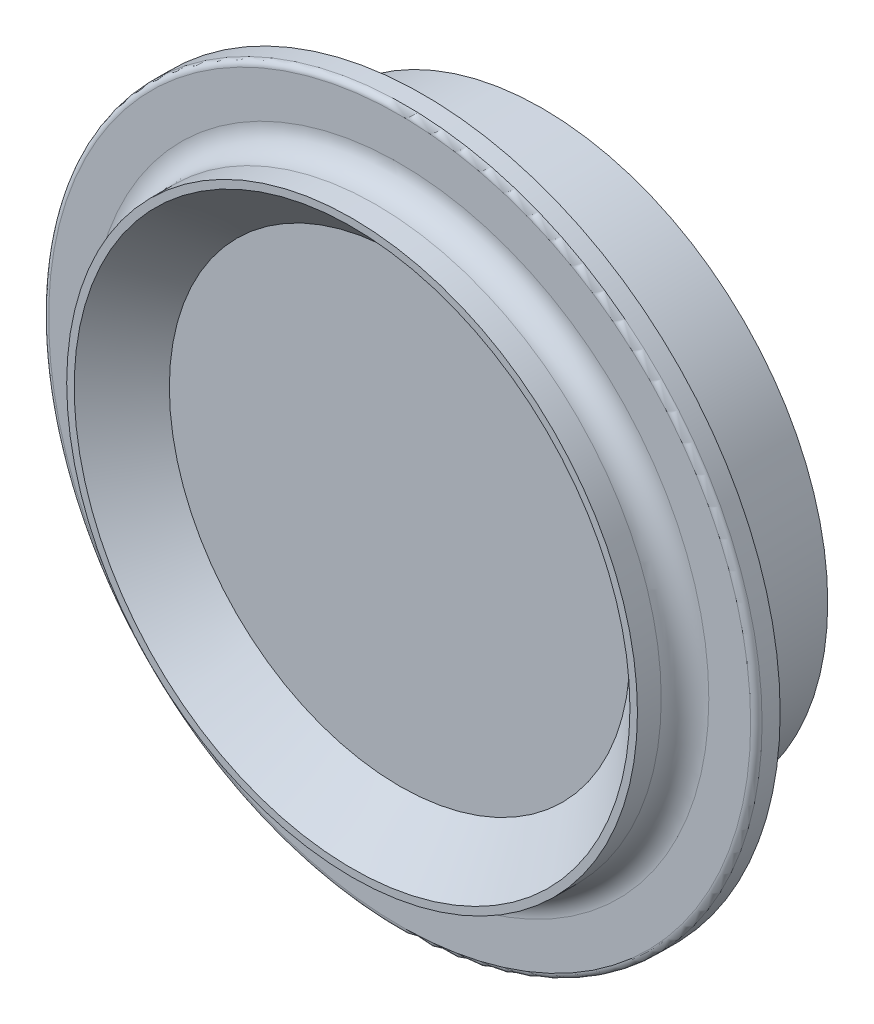
SolidWorks part; units mm, degrees
material "AISI 304"
ref_plane "Front Plane" through (0, 0, 0) normal (0, 0, 1) x (1, 0, 0)
ref_plane "Top Plane" through (0, 0, 0) normal (0, 1, 0) x (1, 0, 0)
ref_plane "Right Plane" through (0, 0, 0) normal (1, 0, 0) x (0, 0, -1)
sketch "Sketch1" plane through (0, 0, 0) normal (0, 0, 1) x (1, 0, 0)
  line L0 (358.31, 263.2027) -> (358.3777, 263.0051)
  line L1 (356.948, 250.8986) -> (358.2723, 250.7125)
  line L2 (358.2581, 250.6141) -> (356.9329, 250.8003)
  line L3 (357.1896, 254.7211) -> (358.5268, 254.7444)
  line L4 (358.5281, 254.645) -> (357.1902, 254.6217)
  line L5 (356.8304, 258.5343) -> (358.1474, 258.7666)
  line L6 (358.1643, 258.6686) -> (356.8464, 258.4362)
  line L7 (323.9266, 279.871) -> (324.1241, 279.9387)
  line L8 (332.4082, 278.7506) -> (332.3848, 280.0878)
  line L9 (332.4842, 280.0891) -> (332.5076, 278.7512)
  line L10 (353.9034, 247.6991) -> (353.8718, 247.5995)
  line L11 (353.8718, 247.5995) -> (355.116, 247.2047)
  line L12 (355.1477, 247.3043) -> (353.9034, 247.6991)
  line L13 (353.093, 245.5279) -> (353.0512, 245.4322)
  line L14 (343.2276, 272.3738) -> (344.5485, 274.6256)
  line L15 (344.7287, 274.52) -> (343.4077, 272.2681)
  line L16 (343.4077, 272.2681) -> (343.2276, 272.3738)
  line L17 (341.8816, 274.5301) -> (342.4208, 275.7188)
  line L18 (342.5159, 275.6757) -> (341.9767, 274.4869)
  line L19 (341.9767, 274.4869) -> (341.8816, 274.5301)
  line L20 (344.5704, 278.6579) -> (344.758, 278.5661)
  line L21 (344.758, 278.5661) -> (343.6107, 276.2211)
  line L22 (343.4231, 276.3128) -> (344.5704, 278.6579)
  line L23 (343.529, 276.2613) -> (344.1153, 277.4633)
  line L24 (344.2045, 277.4193) -> (343.6107, 276.2211)
  line L25 (353.6191, 254.3151) -> (356.2297, 254.2971)
  line L26 (356.2284, 254.0882) -> (353.6177, 254.1063)
  line L27 (353.6177, 254.1063) -> (353.6191, 254.3151)
  line L28 (354.8237, 256.455) -> (354.8135, 256.559)
  line L29 (354.8135, 256.559) -> (356.1126, 256.6864)
  line L30 (356.1229, 256.5825) -> (354.8237, 256.455)
  line L31 (347.6738, 270.7309) -> (348.5539, 271.6948)
  line L32 (348.6311, 271.6245) -> (347.7509, 270.6605)
  line L33 (347.7509, 270.6605) -> (347.6738, 270.7309)
  line L34 (345.9635, 272.1355) -> (345.8795, 272.1975)
  line L35 (345.8795, 272.1975) -> (346.654, 273.2482)
  line L36 (346.7381, 273.1863) -> (345.9635, 272.1355)
  line L37 (355.7611, 259.0098) -> (354.4824, 258.7472)
  line L38 (354.4614, 258.8495) -> (355.7401, 259.1121)
  line L39 (353.8718, 261.0908) -> (355.116, 261.4855)
  line L40 (355.1477, 261.386) -> (353.9034, 260.9912)
  line L41 (354.4824, 258.7472) -> (354.4614, 258.8495)
  line L42 (353.9034, 260.9912) -> (353.8718, 261.0908)
  line L43 (353.093, 263.1624) -> (353.0512, 263.2581)
  line L44 (353.0512, 263.2581) -> (354.2473, 263.7807)
  line L45 (354.2892, 263.6851) -> (353.093, 263.1624)
  line L46 (350.8428, 264.7366) -> (353.1126, 266.0263)
  line L47 (353.2159, 265.8448) -> (350.9459, 264.555)
  line L48 (350.9459, 264.555) -> (350.8428, 264.7366)
  line L49 (349.3744, 269.0066) -> (349.305, 269.0847)
  line L50 (350.816, 267.1921) -> (350.7552, 267.2771)
  line L51 (350.7552, 267.2771) -> (351.8165, 268.037)
  line L52 (351.8774, 267.9521) -> (350.816, 267.1921)
  line L53 (349.305, 269.0847) -> (350.2811, 269.9514)
  line L54 (350.3505, 269.8734) -> (349.3744, 269.0066)
  line L55 (354.4614, 249.8407) -> (355.7401, 249.5782)
  line L56 (355.7611, 249.6805) -> (354.4824, 249.943)
  line L57 (354.4824, 249.943) -> (354.4614, 249.8407)
  line L58 (354.8135, 252.1313) -> (356.1126, 252.0038)
  line L59 (356.1229, 252.1078) -> (354.8237, 252.2352)
  line L60 (354.8237, 252.2352) -> (354.8135, 252.1313)
  line L61 (354.3589, 265.76) -> (355.5397, 266.3878)
  line L62 (355.5861, 266.2999) -> (354.4045, 265.6716)
  line L63 (352.3076, 268.9945) -> (353.3757, 269.7993)
  line L64 (353.4352, 269.7197) -> (352.3665, 268.9143)
  line L65 (349.7756, 271.8683) -> (350.7046, 272.8303)
  line L66 (350.7758, 272.7609) -> (349.8463, 271.7983)
  line L67 (346.8252, 274.3106) -> (347.5922, 275.4061)
  line L68 (347.6735, 275.3487) -> (346.9059, 274.2526)
  line L69 (328.2797, 276.0224) -> (328.0172, 277.3011)
  line L70 (328.1195, 277.3221) -> (328.382, 276.0434)
  line L71 (328.382, 276.0434) -> (328.2797, 276.0224)
  line L72 (323.9669, 274.654) -> (323.8712, 274.6122)
  line L73 (326.0385, 275.4328) -> (325.6437, 276.677)
  line L74 (325.7433, 276.7087) -> (326.1381, 275.4644)
  line L75 (326.1381, 275.4644) -> (326.0385, 275.4328)
  line L76 (324.8849, 277.44) -> (324.4495, 278.7044)
  line L77 (333.041, 277.7894) -> (333.023, 275.1787)
  line L78 (332.8141, 275.1801) -> (332.8322, 277.7907)
  line L79 (330.5703, 276.3745) -> (330.4428, 277.6736)
  line L80 (330.5468, 277.6839) -> (330.6742, 276.3847)
  line L81 (333.023, 275.1787) -> (332.8141, 275.1801)
  line L82 (330.6742, 276.3847) -> (330.5703, 276.3745)
  line L83 (337.4861, 275.9804) -> (337.7663, 277.2553)
  line L84 (337.8683, 277.233) -> (337.5881, 275.958)
  line L85 (337.5881, 275.958) -> (337.4861, 275.9804)
  line L86 (335.1988, 276.3534) -> (335.3443, 277.6506)
  line L87 (335.4481, 277.639) -> (335.3026, 276.3418)
  line L88 (335.3026, 276.3418) -> (335.1988, 276.3534)
  line L89 (339.8209, 275.3375) -> (339.7219, 275.3704)
  line L90 (339.7219, 275.3704) -> (340.1338, 276.609)
  line L91 (340.2329, 276.5761) -> (339.8209, 275.3375)
  line L92 (324.7735, 277.4015) -> (323.9266, 279.871)
  line L93 (324.1241, 279.9387) -> (324.971, 277.4693)
  line L94 (328.5949, 278.3914) -> (328.3627, 279.7084)
  line L95 (328.4607, 279.7253) -> (328.6931, 278.4074)
  line L96 (324.5436, 278.7365) -> (324.971, 277.4693)
  line L97 (336.2307, 278.509) -> (336.4168, 279.8333)
  line L98 (336.5152, 279.8191) -> (336.3289, 278.4939)
  line L99 (339.9683, 277.6723) -> (340.3593, 278.9512)
  line L100 (340.4543, 278.9218) -> (340.063, 277.6421)
  line L101 (356.1113, 247.161) -> (357.3902, 246.77)
  line L102 (357.3608, 246.675) -> (356.0811, 247.0662)
  line L103 (358.3777, 263.0051) -> (355.9083, 262.1582)
  line L104 (355.8405, 262.3558) -> (358.31, 263.2027)
  line L105 (355.879, 262.2444) -> (357.1434, 262.6798)
  line L106 (357.1755, 262.5857) -> (355.9083, 262.1582)
  line L107 (357.0969, 242.5589) -> (357.0051, 242.3713)
  line L108 (343.2276, 236.3165) -> (344.5485, 234.0647)
  line L109 (344.7287, 234.1703) -> (343.4077, 236.4222)
  line L110 (343.4077, 236.4222) -> (343.2276, 236.3165)
  line L111 (341.6417, 228.8193) -> (341.4441, 228.7515)
  line L112 (341.4441, 228.7515) -> (340.5972, 231.221)
  line L113 (340.7948, 231.2888) -> (341.6417, 228.8193)
  line L114 (340.5972, 231.221) -> (340.2891, 232.1331)
  line L115 (340.6834, 231.2503) -> (341.1188, 229.9858)
  line L116 (341.0247, 229.9538) -> (340.5972, 231.221)
  line L117 (344.199, 232.7703) -> (344.8268, 231.5895)
  line L118 (344.7389, 231.5432) -> (344.1106, 232.7247)
  line L119 (349.305, 239.6056) -> (350.2811, 238.7388)
  line L120 (350.3505, 238.8169) -> (349.3744, 239.6836)
  line L121 (350.816, 241.4981) -> (350.7552, 241.4132)
  line L122 (350.9459, 244.1352) -> (350.8428, 243.9536)
  line L123 (350.7552, 241.4132) -> (351.8165, 240.6533)
  line L124 (351.8774, 240.7382) -> (350.816, 241.4981)
  line L125 (350.8428, 243.9536) -> (353.1126, 242.664)
  line L126 (353.2159, 242.8455) -> (350.9459, 244.1352)
  line L127 (349.3744, 239.6836) -> (349.305, 239.6056)
  line L128 (345.8795, 236.4928) -> (346.654, 235.4421)
  line L129 (346.7381, 235.504) -> (345.9635, 236.5547)
  line L130 (345.9635, 236.5547) -> (345.8795, 236.4928)
  line L131 (347.6738, 237.9594) -> (348.5539, 236.9954)
  line L132 (348.6311, 237.0658) -> (347.7509, 238.0298)
  line L133 (347.7509, 238.0298) -> (347.6738, 237.9594)
  line L134 (347.4335, 234.8216) -> (348.2383, 233.7536)
  line L135 (348.1587, 233.6941) -> (347.3533, 234.7628)
  line L136 (350.3073, 237.3537) -> (351.2693, 236.4247)
  line L137 (351.1999, 236.3534) -> (350.2373, 237.283)
  line L138 (352.7496, 240.3041) -> (353.8451, 239.537)
  line L139 (353.7877, 239.4558) -> (352.6916, 240.2233)
  line L140 (354.7003, 243.6002) -> (355.9023, 243.014)
  line L141 (355.8583, 242.9248) -> (354.6556, 243.5114)
  line L142 (357.0051, 242.3713) -> (354.6556, 243.5114)
  line L143 (354.7518, 243.7062) -> (357.0969, 242.5589)
  line L144 (354.2892, 245.0052) -> (353.093, 245.5279)
  line L145 (353.0512, 245.4322) -> (354.2473, 244.9095)
  line L146 (311.6648, 247.6991) -> (311.6964, 247.5995)
  line L147 (311.6964, 247.5995) -> (310.4522, 247.2047)
  line L148 (310.4206, 247.3043) -> (311.6648, 247.6991)
  line L149 (309.7278, 246.3345) -> (307.2583, 245.4876)
  line L150 (309.6893, 246.4459) -> (308.4248, 246.0105)
  line L151 (308.3928, 246.1046) -> (309.6581, 246.5403)
  line L152 (312.4752, 245.5279) -> (312.5171, 245.4322)
  line L153 (312.5992, 263.4426) -> (311.4104, 263.9818)
  line L154 (311.4535, 264.0769) -> (312.6423, 263.5377)
  line L155 (312.8187, 268.3862) -> (311.7232, 269.1532)
  line L156 (311.7805, 269.2345) -> (312.8767, 268.4669)
  line L157 (311.9491, 254.3751) -> (309.3385, 254.3932)
  line L158 (309.3399, 254.602) -> (311.9506, 254.584)
  line L159 (311.1068, 249.8407) -> (309.8282, 249.5782)
  line L160 (309.8071, 249.6805) -> (311.0858, 249.943)
  line L161 (311.0858, 249.943) -> (311.1068, 249.8407)
  line L162 (310.7547, 252.1313) -> (309.4556, 252.0038)
  line L163 (309.4454, 252.1078) -> (310.7445, 252.2352)
  line L164 (310.7445, 252.2352) -> (310.7547, 252.1313)
  line L165 (311.9506, 254.584) -> (311.9491, 254.3751)
  line L166 (311.7588, 261.2829) -> (310.5202, 261.6948)
  line L167 (310.5531, 261.7939) -> (311.7918, 261.3819)
  line L168 (310.7759, 256.7598) -> (309.4786, 256.9053)
  line L169 (309.4902, 257.0091) -> (310.7875, 256.8636)
  line L170 (310.7875, 256.8636) -> (310.7759, 256.7598)
  line L171 (311.1488, 259.0471) -> (309.8739, 259.3273)
  line L172 (309.8963, 259.4293) -> (311.1712, 259.1491)
  line L173 (311.1712, 259.1491) -> (311.1488, 259.0471)
  line L174 (311.7918, 261.3819) -> (311.7588, 261.2829)
  line L175 (308.4714, 266.1314) -> (308.5632, 266.319)
  line L176 (308.5632, 266.319) -> (310.9082, 265.1717)
  line L177 (310.8164, 264.9841) -> (308.4714, 266.1314)
  line L178 (310.868, 265.09) -> (309.666, 265.6763)
  line L179 (309.7099, 265.7655) -> (310.9082, 265.1717)
  line L180 (309.4569, 261.5293) -> (308.178, 261.9203)
  line L181 (308.2075, 262.0153) -> (309.4872, 261.624)
  line L182 (308.6203, 257.7917) -> (307.296, 257.9778)
  line L183 (307.3102, 258.0762) -> (308.6353, 257.8899)
  line L184 (308.7379, 250.1559) -> (307.4209, 249.9237)
  line L185 (307.404, 250.0217) -> (308.7218, 250.2541)
  line L186 (318.1226, 270.9354) -> (318.0446, 270.866)
  line L187 (318.0446, 270.866) -> (317.1778, 271.8421)
  line L188 (317.2559, 271.9115) -> (318.1226, 270.9354)
  line L189 (312.6423, 263.5377) -> (312.5992, 263.4426)
  line L190 (316.3984, 269.2348) -> (315.4344, 270.1149)
  line L191 (315.5048, 270.1921) -> (316.4688, 269.3119)
  line L192 (314.9318, 267.4405) -> (313.8811, 268.215)
  line L193 (313.943, 268.2991) -> (314.9937, 267.5245)
  line L194 (314.7555, 264.7886) -> (312.5037, 266.1095)
  line L195 (312.6093, 266.2897) -> (314.8612, 264.9687)
  line L196 (314.8612, 264.9687) -> (314.7555, 264.7886)
  line L197 (314.9937, 267.5245) -> (314.9318, 267.4405)
  line L198 (316.4688, 269.3119) -> (316.3984, 269.2348)
  line L199 (322.3926, 272.4038) -> (321.103, 274.6736)
  line L200 (321.2845, 274.7769) -> (322.5742, 272.5069)
  line L201 (322.5742, 272.5069) -> (322.3926, 272.4038)
  line L202 (319.8522, 272.3162) -> (319.0923, 273.3775)
  line L203 (319.1772, 273.4384) -> (319.9371, 272.377)
  line L204 (319.9371, 272.377) -> (319.8522, 272.3162)
  line L205 (321.1567, 274.7045) -> (321.2475, 274.7561)
  line L206 (321.3693, 275.9199) -> (320.7414, 277.1007)
  line L207 (320.8294, 277.1471) -> (321.4576, 275.9655)
  line L208 (318.1348, 273.8686) -> (317.3299, 274.9367)
  line L209 (317.4096, 274.9962) -> (318.2149, 273.9275)
  line L210 (315.261, 271.3366) -> (314.299, 272.2656)
  line L211 (314.3683, 272.3368) -> (315.3309, 271.4073)
  line L212 (307.2583, 245.4876) -> (307.1905, 245.6851)
  line L213 (307.1905, 245.6851) -> (309.6581, 246.5403)
  line L214 (308.3786, 253.9692) -> (307.0415, 253.9458)
  line L215 (307.0401, 254.0452) -> (308.3781, 254.0686)
  line L216 (312.3524, 242.8455) -> (314.6223, 244.1352)
  line L217 (313.2606, 239.6958) -> (312.1926, 238.8909)
  line L218 (312.1331, 238.9706) -> (313.2018, 239.7759)
  line L219 (311.2093, 242.9303) -> (310.0285, 242.3024)
  line L220 (309.9822, 242.3904) -> (311.1637, 243.0186)
  line L221 (322.3407, 236.3165) -> (321.0197, 234.0647)
  line L222 (319.6888, 236.4928) -> (318.9142, 235.4421)
  line L223 (318.8302, 235.504) -> (319.6047, 236.5547)
  line L224 (319.6047, 236.5547) -> (319.6888, 236.4928)
  line L225 (317.8944, 237.9594) -> (317.0143, 236.9954)
  line L226 (316.9372, 237.0658) -> (317.8173, 238.0298)
  line L227 (317.8173, 238.0298) -> (317.8944, 237.9594)
  line L228 (316.1939, 239.6836) -> (316.2632, 239.6056)
  line L229 (314.7522, 241.4981) -> (314.813, 241.4132)
  line L230 (314.6223, 244.1352) -> (314.7255, 243.9536)
  line L231 (316.2632, 239.6056) -> (315.2872, 238.7388)
  line L232 (315.2178, 238.8169) -> (316.1939, 239.6836)
  line L233 (314.813, 241.4132) -> (313.7517, 240.6533)
  line L234 (313.6909, 240.7382) -> (314.7522, 241.4981)
  line L235 (314.7255, 243.9536) -> (312.4556, 242.664)
  line L236 (321.0197, 234.0647) -> (320.5366, 233.2319)
  line L237 (315.7927, 236.822) -> (314.8637, 235.86)
  line L238 (314.7924, 235.9293) -> (315.722, 236.8919)
  line L239 (318.7431, 234.3797) -> (317.976, 233.2842)
  line L240 (317.8948, 233.3415) -> (318.6623, 234.4377)
  line L241 (311.2791, 245.0052) -> (312.4752, 245.5279)
  line L242 (312.5171, 245.4322) -> (311.3209, 244.9095)
  line L243 (331.3699, 253.8551) -> (318.8631, 230.9482)
  line L244 (318.8631, 230.9482) -> (333.0431, 252.871)
  line L245 (323.8712, 274.6122) -> (323.3485, 275.8083)
  line L246 (323.4442, 275.8502) -> (323.9669, 274.654)
  arc A0 (320.9175, 234.1243) -> (321.0197, 234.0647) centre (332.7841, 254.3451) ccw
  arc A1 (320.3941, 233.3152) -> (320.5366, 233.2319) centre (332.7841, 254.3451) ccw
  arc A2 (357.3608, 246.675) -> (357.3902, 246.77) centre (332.7841, 254.3451) ccw
  arc A3 (358.2581, 250.6141) -> (358.2723, 250.7125) centre (332.7841, 254.3451) ccw
  arc A4 (358.5281, 254.645) -> (358.5268, 254.7444) centre (332.7841, 254.3451) ccw
  arc A5 (358.1643, 258.6686) -> (358.1474, 258.7666) centre (332.7841, 254.3451) ccw
  arc A6 (357.1755, 262.5857) -> (357.1434, 262.6798) centre (332.7841, 254.3451) ccw
  arc A7 (340.4543, 278.9218) -> (340.3593, 278.9512) centre (332.7841, 254.3451) ccw
  arc A8 (328.4607, 279.7253) -> (328.3627, 279.7084) centre (332.7841, 254.3451) ccw
  arc A9 (336.5152, 279.8191) -> (336.4168, 279.8333) centre (332.7841, 254.3451) ccw
  arc A10 (332.4842, 280.0891) -> (332.3848, 280.0878) centre (332.7841, 254.3451) ccw
  arc A11 (344.2045, 277.4193) -> (344.1153, 277.4633) centre (332.7841, 254.3451) ccw
  arc A12 (355.5861, 266.2999) -> (355.5397, 266.3878) centre (332.7841, 254.3451) ccw
  arc A13 (353.4352, 269.7197) -> (353.3757, 269.7993) centre (332.7841, 254.3451) ccw
  arc A14 (350.7758, 272.7609) -> (350.7046, 272.8303) centre (332.7841, 254.3451) ccw
  arc A15 (347.6735, 275.3487) -> (347.5922, 275.4061) centre (332.7841, 254.3451) ccw
  arc A16 (333.0492, 254.8015) -> (332.5141, 253.8917) centre (332.7841, 254.3451) ccw
  arc A17 (333.184, 255.0166) -> (332.3916, 253.6694) centre (332.7915, 254.3408) ccw
  arc A18 (332.3916, 253.6694) -> (333.184, 255.0166) centre (332.7915, 254.3408) ccw
  arc A19 (332.5141, 253.8917) -> (333.0492, 254.8015) centre (332.7841, 254.3451) ccw
  arc A20 (332.0182, 253.0592) -> (333.5359, 255.6394) centre (332.7841, 254.3451) ccw
  arc A21 (333.5359, 255.6394) -> (332.0182, 253.0592) centre (332.7841, 254.3451) ccw
  arc A22 (332.36, 255.7805) -> (333.7955, 260.768) centre (327.1953, 259.9674) ccw
  arc A23 (337.927, 258.2899) -> (334.2289, 254.7361) centre (340.3283, 252.0901) ccw
  arc A24 (337.927, 258.2899) -> (338.2964, 259.6767) centre (337.6063, 259.1179) ccw
  arc A25 (338.2964, 259.6767) -> (336.7556, 261.0199) centre (333.6861, 255.9435) ccw
  arc A26 (332.0182, 253.0592) -> (333.0431, 252.871) centre (332.7841, 254.3451) ccw
  arc A27 (331.3699, 253.8551) -> (332.0182, 253.0592) centre (332.7841, 254.3451) ccw
  arc A28 (332.36, 255.7805) -> (333.7955, 260.768) centre (327.1953, 259.9674) ccw
  arc A29 (333.5359, 255.6394) -> (332.36, 255.7805) centre (332.7841, 254.3451) ccw
  arc A30 (334.2289, 254.7361) -> (333.5359, 255.6394) centre (332.7841, 254.3451) ccw
  arc A31 (337.927, 258.2899) -> (334.2289, 254.7361) centre (340.3283, 252.0901) ccw
  arc A32 (337.927, 258.2899) -> (338.2964, 259.6767) centre (337.6063, 259.1179) ccw
  arc A33 (338.2964, 259.6767) -> (336.7556, 261.0199) centre (333.6861, 255.9435) ccw
  arc A34 (333.184, 255.0166) -> (332.3916, 253.6694) centre (332.7841, 254.3451) ccw
  arc A35 (332.3916, 253.6694) -> (333.184, 255.0166) centre (332.7841, 254.3451) ccw
  arc A36 (333.0492, 254.8015) -> (332.5141, 253.8917) centre (332.7841, 254.3451) ccw
  arc A37 (332.5141, 253.8917) -> (333.0492, 254.8015) centre (332.7841, 254.3451) ccw
  arc A38 (336.7556, 261.0199) -> (334.8451, 261.7469) centre (333.7223, 255.9218) ccw
  arc A39 (334.8451, 261.7469) -> (333.7955, 260.768) centre (334.677, 260.875) ccw
  arc A40 (336.7556, 261.0199) -> (334.8451, 261.7469) centre (333.7223, 255.9218) ccw
  arc A41 (334.8451, 261.7469) -> (333.7955, 260.768) centre (334.677, 260.875) ccw
  arc A42 (324.5436, 278.7365) -> (324.4495, 278.7044) centre (332.7841, 254.3451) ccw
  arc A43 (341.0247, 229.9538) -> (341.1188, 229.9858) centre (332.7841, 254.3451) ccw
  arc A44 (344.7389, 231.5432) -> (344.8268, 231.5895) centre (332.7841, 254.3451) ccw
  arc A45 (348.1587, 233.6941) -> (348.2383, 233.7536) centre (332.7841, 254.3451) ccw
  arc A46 (351.1999, 236.3534) -> (351.2693, 236.4247) centre (332.7841, 254.3451) ccw
  arc A47 (353.7877, 239.4558) -> (353.8451, 239.537) centre (332.7841, 254.3451) ccw
  arc A48 (355.8583, 242.9248) -> (355.9023, 243.014) centre (332.7841, 254.3451) ccw
  arc A49 (328.9492, 231.5069) -> (328.8256, 230.5113) centre (335.4079, 230.1994) ccw
  circle A50 centre (329.1375, 230.1994) radius 1.7721
  arc A51 (328.8256, 229.8875) -> (328.9492, 228.8919) centre (335.4079, 230.1994) ccw
  arc A52 (327.83, 230.0111) -> (328.8256, 229.8875) centre (329.1375, 236.4697) ccw
  arc A53 (327.83, 230.3877) -> (327.83, 230.0111) centre (329.1375, 230.1994) ccw
  arc A54 (328.8256, 230.5113) -> (327.83, 230.3877) centre (329.1375, 223.929) ccw
  circle A55 centre (325.4397, 240.6033) radius 0.2899
  arc A56 (329.3258, 231.5069) -> (328.9492, 231.5069) centre (329.1375, 230.1994) ccw
  arc A57 (329.3258, 228.8919) -> (329.4494, 229.8875) centre (322.8672, 230.1994) ccw
  arc A58 (330.445, 230.3877) -> (329.4494, 230.5113) centre (329.1375, 223.929) ccw
  arc A59 (328.9492, 228.8919) -> (329.3258, 228.8919) centre (329.1375, 230.1994) ccw
  arc A60 (330.445, 230.0111) -> (330.445, 230.3877) centre (329.1375, 230.1994) ccw
  arc A61 (329.4494, 229.8875) -> (330.445, 230.0111) centre (329.1375, 236.4697) ccw
  arc A62 (329.4494, 230.5113) -> (329.3258, 231.5069) centre (322.8672, 230.1994) ccw
  arc A63 (336.7427, 230.5113) -> (336.619, 231.5069) centre (330.1604, 230.1994) ccw
  arc A64 (336.1188, 230.5113) -> (335.1232, 230.3877) centre (336.4307, 223.929) ccw
  arc A65 (336.1188, 229.8875) -> (336.2425, 228.8919) centre (342.7011, 230.1994) ccw
  arc A66 (336.7427, 229.8875) -> (337.7383, 230.0111) centre (336.4307, 236.4697) ccw
  arc A67 (337.7383, 230.0111) -> (337.7383, 230.3877) centre (336.4307, 230.1994) ccw
  arc A68 (336.2425, 228.8919) -> (336.619, 228.8919) centre (336.4307, 230.1994) ccw
  arc A69 (335.1232, 230.3877) -> (335.1232, 230.0111) centre (336.4307, 230.1994) ccw
  arc A70 (335.1232, 230.0111) -> (336.1188, 229.8875) centre (336.4307, 236.4697) ccw
  arc A71 (337.7383, 230.3877) -> (336.7427, 230.5113) centre (336.4307, 223.929) ccw
  arc A72 (336.619, 228.8919) -> (336.7427, 229.8875) centre (330.1604, 230.1994) ccw
  arc A73 (336.2425, 231.5069) -> (336.1188, 230.5113) centre (342.7011, 230.1994) ccw
  arc A74 (336.619, 231.5069) -> (336.2425, 231.5069) centre (336.4307, 230.1994) ccw
  circle A75 centre (336.4307, 230.1994) radius 1.7721
  arc A76 (308.3928, 246.1046) -> (308.4248, 246.0105) centre (332.7841, 254.3451) ccw
  arc A77 (311.7805, 269.2345) -> (311.7232, 269.1532) centre (332.7841, 254.3451) ccw
  arc A78 (309.7099, 265.7655) -> (309.666, 265.6763) centre (332.7841, 254.3451) ccw
  arc A79 (308.2075, 262.0153) -> (308.178, 261.9203) centre (332.7841, 254.3451) ccw
  arc A80 (307.3102, 258.0762) -> (307.296, 257.9778) centre (332.7841, 254.3451) ccw
  arc A81 (307.404, 250.0217) -> (307.4209, 249.9237) centre (332.7841, 254.3451) ccw
  arc A82 (311.1567, 263.3979) -> (311.0497, 263.1378) centre (332.7841, 254.3451) ccw
  arc A83 (320.8294, 277.1471) -> (320.7414, 277.1007) centre (332.7841, 254.3451) ccw
  arc A84 (317.4096, 274.9962) -> (317.3299, 274.9367) centre (332.7841, 254.3451) ccw
  arc A85 (314.3683, 272.3368) -> (314.299, 272.2656) centre (332.7841, 254.3451) ccw
  arc A86 (307.0401, 254.0452) -> (307.0415, 253.9458) centre (332.7841, 254.3451) ccw
  arc A87 (309.9822, 242.3904) -> (310.0285, 242.3024) centre (332.7841, 254.3451) ccw
  arc A88 (312.1331, 238.9706) -> (312.1926, 238.8909) centre (332.7841, 254.3451) ccw
  arc A89 (314.7924, 235.9293) -> (314.8637, 235.86) centre (332.7841, 254.3451) ccw
  arc A90 (317.8948, 233.3415) -> (317.976, 233.2842) centre (332.7841, 254.3451) ccw
  arc A91 (340.5972, 231.221) -> (320.214, 233.4224) centre (332.7841, 254.3451) ccw
  arc A92 (340.2891, 232.1331) -> (320.6758, 234.2681) centre (332.7841, 254.3451) ccw
  circle A93 centre (332.7841, 254.3451) radius 38.0927
  circle A94 centre (332.7841, 254.3451) radius 37.0909
  circle A95 centre (332.7841, 254.3451) radius 32.2317
sketch "Sketch2" plane through (0, 0, 0) normal (0, 0, 1) x (1, 0, 0)
  circle A0 centre (332.7841, 254.3451) radius 38.0927
extrude "Extrude1" add sketch "Sketch2" against normal blind 25.4
sketch "Sketch3" plane through (0, 0, 0) normal (0, 0, 1) x (1, 0, 0)
  circle A0 centre (332.7841, 254.3451) radius 37.0909
extrude "Extrude2" cut sketch "Sketch3" against normal blind 6.35
chamfer "Chamfer1" distance 6.35 angle 45 1 edges at (369.875, 254.3451, -6.35)
sketch "Sketch10" plane through (0, 0, 0) normal (0, 0, 1) x (1, 0, 0)
  circle A0 centre (332.7841, 254.3451) radius 47.6177
  circle A1 centre (332.7841, 254.3451) radius 38.0927
extrude "Extrude7" add sketch "Sketch10" against normal blind 3.175 from offset 6.35 offset against normal yes
fillet "Fillet1" radius 3.175 1 edges at (370.8769, 254.3451, -6.35)
fillet "Fillet2" radius 0.762 1 edges at (380.4019, 254.3451, -6.35)
